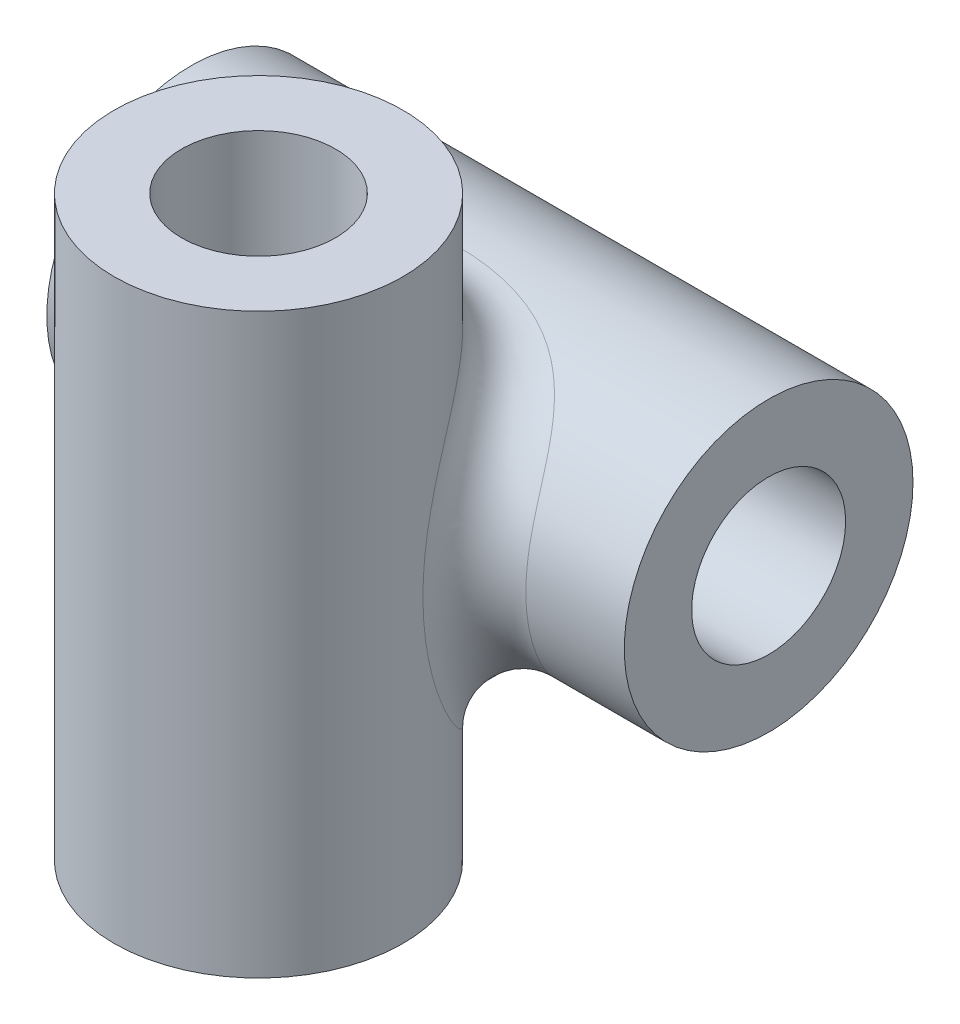
SolidWorks part; units mm, degrees
ref_plane "Front Plane" through (0, 0, 0) normal (0, 0, 1) x (1, 0, 0)
ref_plane "Top Plane" through (0, 0, 0) normal (0, 1, 0) x (1, 0, 0)
ref_plane "Right Plane" through (0, 0, 0) normal (1, 0, 0) x (0, 0, -1)
sketch "Sketch1" plane through (0, 0, 0) normal (0, 1, 0) x (1, 0, 0)
  circle A0 centre (0, 0) radius 8
  circle A1 centre (0, 0) radius 15
  dimension "D1" = 30
  dimension "D2" = 16
extrude "Boss-Extrude1" add sketch "Sketch1" along normal mid plane 60
sketch "Sketch2" plane through (0, 0, 0) normal (1, 0, 0) x (0, 0, -1)
  circle A0 centre (23, 0) radius 8
  circle A1 centre (23, 0) radius 15
  dimension "D1" = 30
  dimension "D2" = 16
  dimension "D3" = 23
extrude "Boss-Extrude2" add sketch "Sketch2" along normal mid plane 60
fillet "Fillet1" radius 5 1 edges at (-3.3823, -12.4366, -14.6137)
